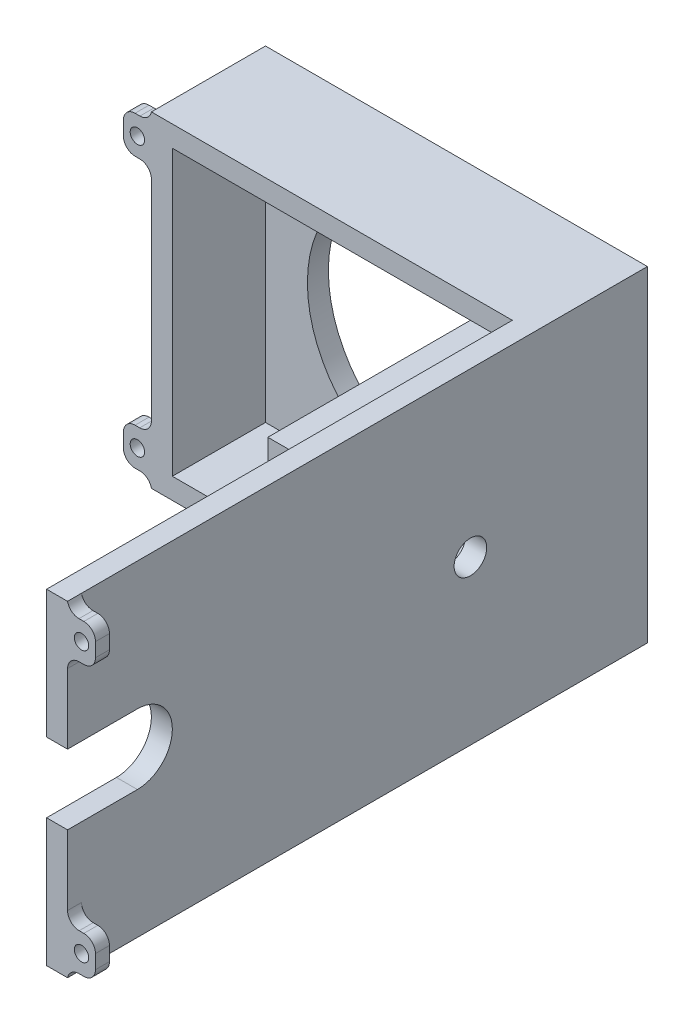
SolidWorks part; units mm, degrees
ref_plane "Front Plane" through (0, 0, 0) normal (1, 0, 0) x (0, 1, 0)
ref_plane "Top Plane" through (0, 0, 0) normal (0, 0, 1) x (0, 1, 0)
ref_plane "Right Plane" through (0, 0, 0) normal (0, 1, 0) x (-1, 0, 0)
sketch "Sketch1" plane through (0, 0, 0) normal (0, 0, 1) x (0, 1, 0)
  line L1 (-35, -41) -> (35, -41)
  line L2 (-35, -41) -> (-35, 41)
  line L3 (-35, 41) -> (35, 41)
  line L4 (35, -41) -> (35, 41)
  line L5 (-35, -41) -> (35, 41) construction
  line L6 (-35, 41) -> (35, -41) construction
  point P0 (0, 0)
  dimension "D1" = 70
  dimension "D2" = 82
extrude "Boss-Extrude1" add sketch "Sketch1" along normal blind 4.5
sketch "Sketch2" plane through (0, 0, 4.5) normal (0, 0, 1) x (1, 0, 0)
  line L0 (41, 35) -> (-41, 35) construction
  line L1 (41, -35) -> (36.5, -35)
  line L2 (41, -35) -> (41, 35)
  line L3 (41, 35) -> (36.5, 35)
  line L4 (36.5, -35) -> (36.5, 35)
  dimension "D1" = 4.5
extrude "Boss-Extrude2" add sketch "Sketch2" along normal blind 120
sketch "Sketch3" plane through (0, 0, 4.5) normal (0, 0, 1) x (1, 0, 0)
  line L0 (36.5, 35) -> (-41, 35)
  line L1 (-41, 35) -> (-41, -35)
  line L2 (-41, -35) -> (36.5, -35)
  line L3 (36.5, -35) -> (36.5, -30.5)
  line L4 (36.5, 35) -> (36.5, -35) construction
  line L5 (36.5, -30.5) -> (-36.5, -30.5)
  line L6 (-36.5, -30.5) -> (-36.5, 30.5)
  line L7 (-36.5, 30.5) -> (36.5, 30.5)
  line L8 (36.5, 30.5) -> (36.5, 35)
  dimension "D1" = 4.5
  dimension "D2" = 4.5
extrude "Boss-Extrude3" add sketch "Sketch3" along normal blind 20
sketch "Sketch4" plane through (0, 0, 0) normal (0, 0, -1) x (1, 0, 0)
  circle A0 centre (0, 0) radius 27.5
  dimension "D1" = 55
extrude "Cut-Extrude1" cut sketch "Sketch4" against normal up to next
sketch "Sketch5" plane through (36.5, 0, 0) normal (-1, 0, 0) x (0, -1, 0)
  line L0 (0, 124.5) -> (0, 0) construction
  line L1 (-35, 124.5) -> (35, 124.5) construction
  line L3 (-7.5, 124.5) -> (7.5, 124.5)
  line L4 (7.5, 124.5) -> (7.5, 109.5)
  line L5 (-7.5, 109.5) -> (-7.5, 124.5)
  line L6 (-35, 0) -> (35, 0) construction
  arc A0 (7.5, 109.5) -> (-7.5, 109.5) centre (0, 109.5) cw
  circle A1 centre (0, 38) radius 3.5
  point P4 (0, 0)
  dimension "D2" = 15
  dimension "D3" = 7
  dimension "D1" = 15
  dimension "D4" = 38
extrude "Cut-Extrude2" cut sketch "Sketch5" against normal up to next
sketch "Sketch6" plane through (0, 0, 124.5) normal (0, 0, 1) x (1, 0, 0)
  line L0 (36.5, 0) -> (41, 0) construction
  line L1 (36.5, 30.5) -> (36.5, -30.5) construction
  line L2 (41, -7.5) -> (41, 7.5) construction
  line L3 (41, 7.5) -> (41, 35) construction
  line L4 (41, 33) -> (47, 33)
  line L5 (41, 33) -> (41, 25)
  line L6 (41, 25) -> (47, 25)
  line L7 (47, 33) -> (47, 25)
  line L8 (41, -25) -> (47, -25)
  line L9 (47, -33) -> (47, -25)
  line L10 (41, -33) -> (47, -33)
  line L11 (41, -33) -> (41, -25)
  dimension "D1" = 25
  dimension "D2" = 8
  dimension "D3" = 6
extrude "Boss-Extrude4" add sketch "Sketch6" against normal blind 3
sketch "Sketch7" plane through (0, 0, 24.5) normal (0, 0, 1) x (1, 0, 0)
  line L0 (-41, 0) -> (-36.5, 0) construction
  line L1 (-41, 35) -> (-41, -35) construction
  line L2 (-36.5, -30.5) -> (-36.5, 30.5) construction
  line L3 (-41, -25) -> (-47, -25)
  line L4 (-41, 33) -> (-47, 33)
  line L5 (-41, 33) -> (-41, 25)
  line L6 (-41, 25) -> (-47, 25)
  line L7 (-47, 33) -> (-47, 25)
  line L8 (-47, -33) -> (-47, -25)
  line L9 (-41, -33) -> (-47, -33)
  line L10 (-41, -33) -> (-41, -25)
  dimension "D1" = 25
  dimension "D2" = 8
  dimension "D3" = 6
extrude "Boss-Extrude5" add sketch "Sketch7" against normal blind 3
sketch "Sketch8" plane through (0, 0, 24.5) normal (0, 0, 1) x (1, 0, 0)
  line L0 (-44, 33) -> (-44, 25) construction
  line L1 (-41, 33) -> (-47, 33) construction
  line L2 (-47, 25) -> (-41, 25) construction
  line L3 (-44, -25) -> (-44, -33) construction
  line L4 (-41, -25) -> (-47, -25) construction
  line L5 (-47, -33) -> (-41, -33) construction
  line L6 (44, 33) -> (44, 25) construction
  line L7 (47, 33) -> (41, 33) construction
  line L8 (41, 25) -> (47, 25) construction
  line L9 (44, -25) -> (44, -33) construction
  line L10 (47, -25) -> (41, -25) construction
  line L11 (41, -33) -> (47, -33) construction
  circle A0 centre (-44, 29) radius 1.55
  circle A1 centre (44, 29) radius 1.55
  circle A2 centre (44, -29) radius 1.55
  circle A3 centre (-44, -29) radius 1.55
  dimension "D1" = 3.1
extrude "Cut-Extrude4" cut sketch "Sketch8" against normal through all and the other way through all
fillet "Fillet1" radius 2.5 16 edges at (41, 33, 123) (47, 33, 123) (47, 25, 123) (41, 25, 123) (41, -33, 123) (41, -25, 123) (47, -25, 123) (47, -33, 123) (-41, -33, 23) (-47, -33, 23) (-47, -25, 23) (-41, -25, 23) (-41, 33, 23) (-47, 25, 23) (-41, 25, 23) (-47, 33, 23)
sketch "Sketch9" plane through (36.5, 0, 0) normal (-1, 0, 0) x (0, -1, 0)
  line L0 (-30.5, 24.5) -> (-30.5, 68)
  line L1 (-30.5, 68) -> (30.5, 68)
  line L2 (30.5, 68) -> (30.5, 24.5)
  line L4 (-15.25, 17.75) -> (15.25, 17.75)
  line L5 (-15.25, 17.75) -> (-15.25, 58.25)
  line L6 (-15.25, 58.25) -> (15.25, 58.25)
  line L7 (15.25, 17.75) -> (15.25, 58.25)
  line L8 (-15.25, 17.75) -> (15.25, 58.25) construction
  line L9 (-15.25, 58.25) -> (15.25, 17.75) construction
  line L11 (-7.5, 109.5) -> (-7.5, 124.5)
  line L12 (-7.5, 124.5) -> (-35, 124.5)
  line L13 (-35, 124.5) -> (-35, 24.5)
  line L14 (-35, 24.5) -> (-30.5, 24.5)
  line L15 (-30.5, 24.5) -> (-30.5, 4.5)
  line L16 (-30.5, 4.5) -> (30.5, 4.5)
  line L17 (30.5, 4.5) -> (30.5, 24.5)
  line L18 (30.5, 24.5) -> (35, 24.5)
  line L19 (35, 24.5) -> (35, 124.5)
  line L20 (35, 124.5) -> (7.5, 124.5)
  line L21 (7.5, 124.5) -> (7.5, 109.5)
  line L26 (-30.5, 24.5) -> (-30.5, 4.5)
  line L27 (-30.5, 4.5) -> (30.5, 4.5)
  line L28 (30.5, 4.5) -> (30.5, 24.5)
  circle A0 centre (0, 38) radius 3.5 construction
  arc A1 (-7.5, 109.5) -> (7.5, 109.5) centre (0, 109.5) ccw
  point P11 (0, 38)
  dimension "D2" = 30
  dimension "D3" = 40.5
  dimension "D4" = 30.5
  dimension "D1" = 0
extrude "Boss-Extrude6" add sketch "Sketch9" along normal blind 9
